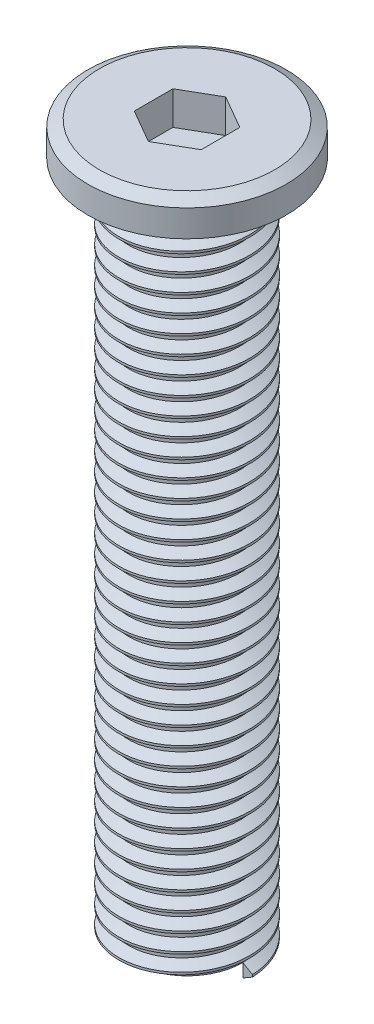
SolidWorks part; units mm, degrees
ref_plane "Front Plane" through (0, 0, 0) normal (0, 0, 1) x (1, 0, 0)
ref_plane "Top Plane" through (0, 0, 0) normal (0, 1, 0) x (1, 0, 0)
ref_plane "Right Plane" through (0, 0, 0) normal (1, 0, 0) x (0, 0, -1)
sketch "Sketch1" plane through (0, 0, 0) normal (0, 1, 0) x (1, 0, 0)
  circle A0 centre (0, 0) radius 4.45
  dimension "D1" = 8.9
extrude "Boss-Extrude1" add sketch "Sketch1" along normal blind 1.5
chamfer "Chamfer2" distance 0.3 angle 60 1 edges at (0, 1.5, 4.45)
sketch "Sketch8" plane through (0, 1.5, 0) normal (0, 1, 0) x (1, 0, 0)
  line L1 (0, 1.7321) -> (-1.5, 0.866)
  line L2 (-1.5, 0.866) -> (-1.5, -0.866)
  line L3 (-1.5, -0.866) -> (0, -1.7321)
  line L4 (0, -1.7321) -> (1.5, -0.866)
  line L5 (1.5, -0.866) -> (1.5, 0.866)
  line L6 (1.5, 0.866) -> (0, 1.7321)
  circle A0 centre (0, 0) radius 1.5 construction
  dimension "D1" = 3
  dimension "D2" = 1.5
extrude "Cut-Extrude1" cut sketch "Sketch8" against normal blind 3
sketch "Sketch3" plane through (0, 0, 0) normal (0, -1, 0) x (1, 0, 0)
  circle A0 centre (0, 0) radius 2.5
  dimension "D1" = 5
extrude "Boss-Extrude2" add sketch "Sketch3" along normal blind 30
thread "Thread1" pitch 0.8 profile "Thread Profile2" start angle 0, offset 0, length 0, pitch 0.8, diameter 5
ref_plane "Plane2" through (-2.5, 0, 0) normal (0, 0, 1) x (-1, 0, 0)
sketch "Thread Profile2" plane through (-2.5, 0, 0) normal (0, 0, 1) x (-1, 0, 0)
  line L0 (0, 0) -> (0, 0.8) construction
  line L1 (0, 0) -> (0.433, 0.25)
  line L2 (0.433, 0.25) -> (0.433, 0.35)
  line L3 (0.433, 0.35) -> (0, 0.6)
  line L4 (0.433, 0.3) -> (0, 0.3) construction
  line L11 (0, 0) -> (0, 0.6)
  point P2 (0, 0)
  dimension "Pitch" = 0.8
  dimension "Profile_Angle" = 60
  dimension "Profile_Land" = 0.1
  dimension "Profile_Height" = 0.433
